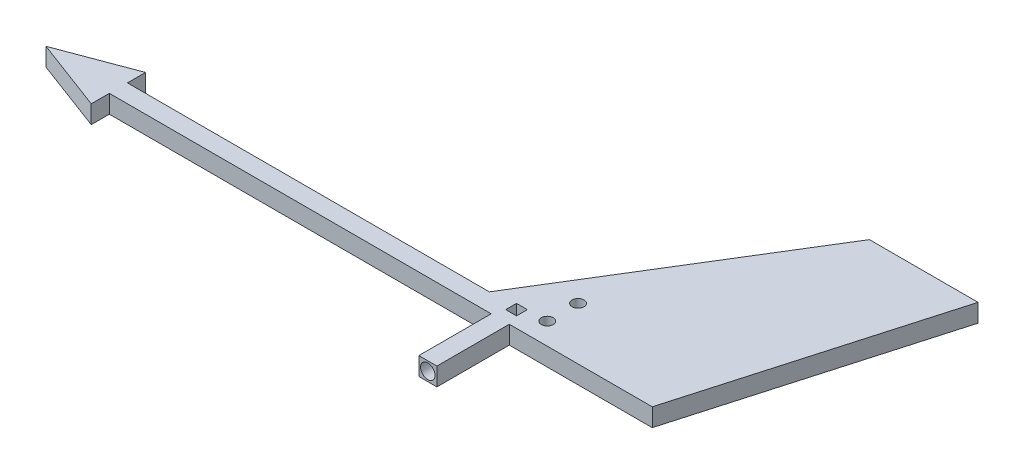
SolidWorks part; units mm, degrees
ref_plane "Front Plane" through (0, 0, 0) normal (0, 0, 1) x (1, 0, 0)
ref_plane "Top Plane" through (0, 0, 0) normal (0, 1, 0) x (1, 0, 0)
ref_plane "Right Plane" through (0, 0, 0) normal (1, 0, 0) x (0, 0, -1)
other "Center of Mass"
sketch "Sketch1" plane through (0, 0, 0) normal (0, 1, 0) x (1, 0, 0)
  line L0 (-20, 0) -> (0, 7.5)
  line L1 (-20, 0) -> (0, -7.5)
  line L2 (0, -7.5) -> (0, 7.5) construction
  line L3 (0, 7.5) -> (0, 2.5)
  line L4 (0, 2.5) -> (100, 2.5)
  line L5 (0, -7.5) -> (0, -2.5)
  line L6 (0, -2.5) -> (150, -2.5)
  line L7 (150, -2.5) -> (170, 67.5)
  line L8 (170, 67.5) -> (140, 67.5)
  line L9 (140, 67.5) -> (100, 2.5)
  point P2 (0, 0)
  dimension "D1" = 150
  dimension "D2" = 100
  dimension "D3" = 70
  dimension "D4" = 20
  dimension "D5" = 40
  dimension "D6" = 20
  dimension "D7" = 15
  dimension "D8" = 5
extrude "Boss-Extrude1" add sketch "Sketch1" along normal mid plane 5
sketch "Sketch2" plane through (0, -2.5, 0) normal (0, 1, 0) x (1, 0, 0)
  line L0 (118.2332, 12) -> (116.6166, 14.8)
  line L2 (116.6166, 14.8) -> (113.3834, 14.8)
  line L5 (113.3834, 9.2) -> (116.6166, 9.2)
  line L6 (116.6166, 9.2) -> (118.2332, 12)
  line L8 (113.3834, 14.8) -> (111.7668, 12)
  line L9 (111.7668, 12) -> (113.3834, 9.2)
  line L12 (0, -2.5) -> (150, -2.5) construction
  line L13 (118.2332, 3.5) -> (116.6166, 6.3)
  line L14 (116.6166, 6.3) -> (113.3834, 6.3)
  line L15 (113.3834, 6.3) -> (111.7668, 3.5)
  line L16 (111.7668, 3.5) -> (113.3834, 0.7)
  line L17 (113.3834, 0.7) -> (116.6166, 0.7)
  line L18 (116.6166, 0.7) -> (118.2332, 3.5)
  line L19 (118.2332, 12) -> (116.6166, 14.8) [skipped]
  line L20 (113.3834, 14.8) -> (111.7668, 12) [skipped]
  line L21 (111.7668, 12) -> (113.3834, 9.2) [skipped]
  circle A0 centre (115, 12) radius 2.8 construction
  circle A1 centre (115, 12) radius 2.8 construction
  circle A2 centre (115, 3.5) radius 2.8 construction
  point P1 (115, 12)
  point P2 (115, 3.5)
  dimension "D3" = 6
  dimension "D6" = 5.6
  dimension "D5" = 8.5
  dimension "D7" = 15
extrude "Cut-Extrude2" cut sketch "Sketch2" along normal blind 2.5
sketch "Sketch3" plane through (0, 0, 2.5) normal (0, 0, 1) x (1, 0, 0)
  line L1 (105.5, -2.5) -> (110.5, -2.5)
  line L2 (105.5, -2.5) -> (105.5, 2.5)
  line L3 (105.5, 2.5) -> (110.5, 2.5)
  line L4 (110.5, -2.5) -> (110.5, 2.5)
  line L5 (105.5, -2.5) -> (110.5, 2.5) construction
  line L6 (105.5, 2.5) -> (110.5, -2.5) construction
  line L7 (0, 2.5) -> (150, 2.5) construction
  line L8 (0, -2.5) -> (150, -2.5) construction
  point P0 (108, 0)
  dimension "D1" = 5
  dimension "D2" = 108
extrude "Boss-Extrude2" add sketch "Sketch3" along normal blind 20
sketch "Sketch4" plane through (0, 0, 22.5) normal (0, 0, 1) x (1, 0, 0)
  line L0 (105.5, 0) -> (110.5, 0) construction
  line L1 (105.5, 2.5) -> (105.5, -2.5) construction
  line L2 (110.5, -2.5) -> (110.5, 2.5) construction
  circle A0 centre (108, 0) radius 2
  dimension "D1" = 4
extrude "Cut-Extrude3" cut sketch "Sketch4" against normal blind 23
sketch "Sketch6" plane through (0, 2.5, 0) normal (0, 1, 0) x (1, 0, 0)
  line L0 (105.5, -2.5) -> (110.5, -2.5) construction
  line L1 (106.5, 0.5) -> (109.5, 0.5)
  line L2 (106.5, 0.5) -> (106.5, 3.5)
  line L3 (106.5, 3.5) -> (109.5, 3.5)
  line L4 (109.5, 0.5) -> (109.5, 3.5)
  line L5 (106.5, 0.5) -> (109.5, 3.5) construction
  line L6 (106.5, 3.5) -> (109.5, 0.5) construction
  point P0 (108, 2)
  point P5 (108, -2.5)
  dimension "D1" = 3
  dimension "D2" = 3
  dimension "D3" = 3
extrude "Cut-Extrude5" cut sketch "Sketch6" against normal blind 4.5
sketch "Sketch7" plane through (0, 2.5, 0) normal (0, 1, 0) x (1, 0, 0)
  line L0 (110.5, -2.5) -> (150, -2.5) construction
  circle A0 centre (115, 3.5) radius 1.65
  circle A1 centre (115, 12) radius 1.65
  dimension "D1" = 3.3
  dimension "D2" = 3.3
  dimension "D3" = 6
  dimension "D4" = 8.5
  dimension "D5" = 15
extrude "Cut-Extrude6" cut sketch "Sketch7" against normal through all
